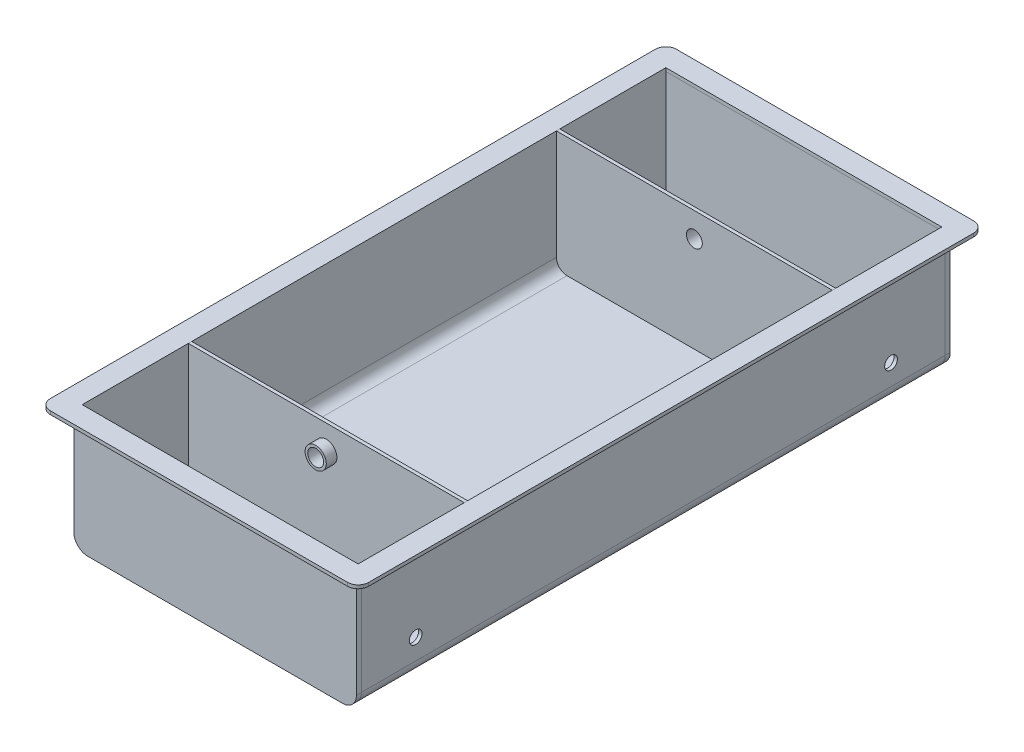
SolidWorks part; units mm, degrees
material "5052-H32"
ref_plane "Front Plane" through (0, 0, 0) normal (0, 0, 1) x (1, 0, 0)
ref_plane "Top Plane" through (0, 0, 0) normal (0, 1, 0) x (1, 0, 0)
ref_plane "Right Plane" through (0, 0, 0) normal (1, 0, 0) x (0, 0, -1)
sketch "Sketch2" plane through (0, 0, 0) normal (0, 0, 1) x (1, 0, 0)
  line L0 (-130, 0) -> (130, 0)
  line L1 (-130, 0) -> (-130, 110)
  line L2 (130, 0) -> (130, 110)
  line L3 (-133.175, -3.175) -> (-133.175, 110)
  line L4 (-133.175, -3.175) -> (133.175, -3.175)
  line L5 (133.175, -3.175) -> (133.175, 110)
  line L6 (-133.175, 110) -> (-130, 110)
  line L7 (130, 110) -> (133.175, 110)
  point P4 (0, 0)
  dimension "D1" = 260
  dimension "D3" = 110
  dimension "D4" = 110
  dimension "D2" = 3.175
  dimension "D5" = 3.175
  dimension "D6" = 3.175
extrude "Interior Dim" add sketch "Sketch2" against normal blind 550
fillet "Fillet2" radius 10 2 edges at (-130, 0, -275) (130, 0, -275)
fillet "Fillet3" radius 13.175 2 edges at (-133.175, -3.175, -275) (133.175, -3.175, -275)
ref_plane "Plane1" through (0, 0, 0) normal (0, 0, 1) x (1, 0, 0)
sketch "Sketch4" plane through (0, 0, 0) normal (0, 0, 1) x (1, 0, 0)
  line L0 (-130, 110) -> (130, 110)
  line L9 (-120, -3.175) -> (120, -3.175)
  line L10 (133.175, 10) -> (133.175, 110)
  line L11 (133.175, 110) -> (130, 110)
  line L12 (130, 110) -> (130, 10)
  line L13 (120, 0) -> (-120, 0)
  line L14 (-130, 10) -> (-130, 110)
  line L15 (-130, 110) -> (-133.175, 110)
  line L16 (-133.175, 110) -> (-133.175, 10)
  line L17 (-120, -3.175) -> (120, -3.175)
  line L18 (133.175, 10) -> (133.175, 110)
  line L19 (133.175, 110) -> (130, 110)
  line L23 (-130, 110) -> (-133.175, 110)
  line L24 (-133.175, 110) -> (-133.175, 10)
  arc A4 (120, -3.175) -> (133.175, 10) centre (120, 10) ccw
  arc A5 (120, 0) -> (130, 10) centre (120, 10) ccw
  arc A6 (-130, 10) -> (-120, 0) centre (-120, 10) ccw
  arc A7 (120, -3.175) -> (133.175, 10) centre (120, 10) ccw
  arc A9 (-133.175, 10) -> (-120, -3.175) centre (-120, 10) ccw
  arc A10 (-133.175, 10) -> (-120, -3.175) centre (-120, 10) ccw
  dimension "D1" = 0
extrude "Endcap1" add sketch "Sketch4" along normal blind 4.7625 separate body
ref_plane "Plane2" through (0, 0, -550) normal (0, 0, -1) x (-1, 0, 0)
sketch "Sketch5" plane through (0, 0, -550) normal (0, 0, -1) x (-1, 0, 0)
  line L8 (133.175, 110) -> (-133.175, 110)
  line L16 (-133.175, 110) -> (-133.175, 10)
  line L17 (-120, -3.175) -> (120, -3.175)
  line L18 (133.175, 10) -> (133.175, 110)
  line L19 (133.175, 110) -> (130, 110)
  line L20 (130, 110) -> (130, 10)
  line L21 (120, 0) -> (-120, 0)
  line L22 (-130, 10) -> (-130, 110)
  line L23 (-130, 110) -> (-133.175, 110)
  line L24 (-133.175, 110) -> (-133.175, 10)
  line L25 (-120, -3.175) -> (120, -3.175)
  line L26 (133.175, 10) -> (133.175, 110)
  arc A6 (-133.175, 10) -> (-120, -3.175) centre (-120, 10) ccw
  arc A7 (-133.175, 10) -> (-120, -3.175) centre (-120, 10) ccw
  arc A8 (120, 0) -> (130, 10) centre (120, 10) ccw
  arc A9 (-130, 10) -> (-120, 0) centre (-120, 10) ccw
  arc A12 (120, -3.175) -> (133.175, 10) centre (120, 10) ccw
  arc A13 (120, -3.175) -> (133.175, 10) centre (120, 10) ccw
  dimension "D1" = 0
ref_plane "Compartment1" through (0, 0, -100) normal (0, 0, -1) x (-1, 0, 0)
sketch "Sketch7" plane through (0, 0, -100) normal (0, 0, -1) x (-1, 0, 0)
  line L1 (130, 110) -> (-130, 110)
  line L10 (-120, -3.175) -> (120, -3.175)
  line L11 (-133.175, 110) -> (-133.175, 10)
  line L12 (-130, 110) -> (-133.175, 110)
  line L13 (-130, 10) -> (-130, 110)
  line L14 (120, 0) -> (-120, 0)
  line L15 (130, 110) -> (130, 10)
  line L16 (133.175, 110) -> (130, 110)
  line L17 (133.175, 10) -> (133.175, 110)
  line L21 (-130, 10) -> (-130, 110)
  line L22 (120, 0) -> (-120, 0)
  line L23 (130, 110) -> (130, 10)
  arc A5 (-130, 10) -> (-120, 0) centre (-120, 10) ccw
  arc A6 (120, 0) -> (130, 10) centre (120, 10) ccw
  arc A7 (-133.175, 10) -> (-120, -3.175) centre (-120, 10) ccw
  arc A8 (120, -3.175) -> (133.175, 10) centre (120, 10) ccw
  arc A9 (-130, 10) -> (-120, 0) centre (-120, 10) ccw
  arc A10 (120, 0) -> (130, 10) centre (120, 10) ccw
  dimension "D1" = 0
extrude "Compartment1_Boss" add sketch "Sketch7" along normal blind 3.175 separate body contours L22 A10 L23 L1 L21 A9 region at (0, 55.0793, -100)
ref_plane "Plane5" through (0, 110, 0) normal (0, 1, 0) x (1, 0, 0)
sketch "Sketch9" plane through (0, 110, 0) normal (0, 1, 0) x (1, 0, 0)
  line L0 (62.2463, 550) -> (-62.2463, 550) construction
  line L1 (-130, 550) -> (130, 550)
  line L2 (-130, 550) -> (-130, 0)
  line L3 (-130, 0) -> (130, 0)
  line L4 (130, 550) -> (130, 0)
  line L5 (-130, 0) -> (-130, 550) construction
  line L6 (-62.2463, 0) -> (62.2463, 0) construction
  line L7 (130, 550) -> (130, 0) construction
  line L8 (-150, 570) -> (-150, -20)
  line L9 (-150, -20) -> (150, -20)
  line L10 (150, 570) -> (150, -20)
  line L11 (-150, 570) -> (150, 570)
extrude "Lid_Flange" add sketch "Sketch9" along normal blind 3.175 separate body contours L11 L8 L9 L10 L1 L4 region at (0, 110, -563.3811)
fillet "Fillet4" radius 10 4 edges at (-150, 111.5875, -570) (150, 111.5875, -570) (150, 111.5875, 20) (-150, 111.5875, 20)
extrude "Endcap2" add sketch "Sketch5" along normal blind 4.7625 separate body
ref_plane "Compartment2" through (0, 0, -450) normal (0, 0, 1) x (1, 0, 0)
sketch "Sketch13" plane through (0, 0, -450) normal (0, 0, 1) x (1, 0, 0)
  line L0 (130, 110) -> (-130, 110)
  line L1 (133.175, 110) -> (130, 110) construction
  line L2 (130, 110) -> (130, 10) construction
  line L3 (-140, 110) -> (140, 110) construction
  line L4 (-130, 10) -> (-130, 110) construction
  line L5 (130, 110) -> (130, 10)
  line L6 (-130, 110) -> (-130, 10)
  line L7 (120, 0) -> (-120, 0)
  arc A0 (120, 0) -> (130, 10) centre (120, 10) ccw construction
  arc A1 (-130, 10) -> (-120, 0) centre (-120, 10) ccw construction
  arc A2 (-130, 10) -> (-120, 0) centre (-120, 10) ccw
  arc A3 (130, 10) -> (120, 0) centre (120, 10) cw
  dimension "D1" = 110
extrude "Compartment2_Boss" add sketch "Sketch13" along normal blind 3.175
sketch "Sketch16" plane through (-133.175, 0, 0) normal (-1, 0, 0) x (0, 0, 1)
  line L0 (-550, 0) -> (-450, 0) construction
  line L1 (-550, 110) -> (-550, 10) construction
  line L2 (0, 110) -> (0, 10) construction
  line L3 (-51, 29.5) -> (-499, 29.5) construction
  circle A0 centre (-499, 29.5) radius 6
  circle A1 centre (-51, 29.5) radius 6
  dimension "D1" = 12
  dimension "D4" = 12
  dimension "D2" = 29.5
  dimension "D3" = 51
  dimension "D5" = 51
extrude "Bearing_holes" cut sketch "Sketch16" against normal through all
sketch "Sketch17" plane through (0, 0, -450) normal (0, 0, -1) x (-1, 0, 0)
  line L0 (142.7388, 110) -> (-142.7388, 110) construction
  line L1 (130, 110) -> (130, 10) construction
  circle A0 centre (0, 90) radius 7.5
  circle A1 centre (0, 90) radius 10
  dimension "D1" = 15
  dimension "D4" = 20
  dimension "D2" = 20
  dimension "D3" = 130
extrude "Wire_Passthrough" cut sketch "Sketch17" against normal up to surface (350 mm away) contours A0 region at (0, 90, -450) up to face at (0, 39.3096, -100)
sketch "Sketch18" plane through (0, 110, 0) normal (0, 1, 0) x (1, 0, 0)
  line L1 (-130, 450) -> (130, 450)
  line L2 (-130, 450) -> (-130, 446.825)
  line L3 (-130, 446.825) -> (130, 446.825)
  line L4 (130, 450) -> (130, 446.825)
  line L5 (-130, 103.175) -> (130, 103.175)
  line L6 (-130, 103.175) -> (-130, 100)
  line L7 (-130, 100) -> (130, 100)
  line L8 (130, 103.175) -> (130, 100)
extrude "Boss-Extrude1" add sketch "Sketch18" along normal blind 3.18
extrude "Wire_Tube_2" add sketch "Sketch17<3>" along normal blind 10
sketch "Sketch17<3>" plane through (0, 0, -450) normal (0, 0, -1) x (-1, 0, 0) same geometry as "Sketch17"
sketch "Sketch19" plane through (0, 0, -100) normal (0, 0, 1) x (1, 0, 0)
  circle A0 centre (0, 90) radius 10
  circle M1 centre (0, 90) radius 7.5
  dimension "D1" = 20
extrude "Wire_Tube_1" add sketch "Sketch19" along normal blind 10 contours A0 M1 region at (-9.7172, 90, -100)
sketch "Sketch20" plane through (0, 110, 175) normal (0, 1, 0) x (1, 0, 0)
  line L0 (130, 450) -> (-130, 450) construction
  line L1 (-130, 725) -> (130, 725) construction
  line L2 (-130, 725) -> (-130, 175) construction
  line L3 (-130, 175) -> (130, 175) construction
  line L4 (130, 725) -> (130, 175) construction
  line L5 (130, 621.825) -> (130, 278.175) construction
  line L7 (0, 450) -> (0, 175) construction
  line L8 (-150, 745) -> (-150, 155) construction
  line L9 (-150, 155) -> (150, 155) construction
  line L10 (150, 745) -> (150, 155) construction
  line L11 (-150, 745) -> (150, 745) construction
  line L12 (-130, 621.825) -> (-130, 278.175) construction
  circle A0 centre (-140, 165) radius 2.5
  circle A2 centre (-140, 217) radius 2.5
  circle A3 centre (-140, 269) radius 2.5
  circle A4 centre (-140, 321) radius 2.5
  circle A5 centre (-140, 373) radius 2.5
  circle A6 centre (-140, 425) radius 2.5
  circle A7 centre (-140, 477) radius 2.5
  circle A8 centre (-140, 529) radius 2.5
  circle A9 centre (-140, 581) radius 2.5
  circle A10 centre (-140, 633) radius 2.5
  circle A16 centre (-140, 685) radius 2.5
  circle A17 centre (-84, 685) radius 2.5
  circle A18 centre (-28, 685) radius 2.5
  circle A19 centre (28, 685) radius 2.5
  circle A20 centre (84, 685) radius 2.5
  circle A21 centre (140, 685) radius 2.5
  circle A22 centre (140, 633) radius 2.5
  circle A23 centre (140, 581) radius 2.5
  circle A24 centre (140, 529) radius 2.5
  circle A25 centre (140, 477) radius 2.5
  circle A26 centre (140, 425) radius 2.5
  circle A27 centre (140, 373) radius 2.5
  circle A28 centre (140, 321) radius 2.5
  circle A29 centre (140, 269) radius 2.5
  circle A30 centre (140, 217) radius 2.5
  circle A31 centre (140, 165) radius 2.5
  circle A37 centre (84, 165) radius 2.5
  circle A38 centre (28, 165) radius 2.5
  circle A39 centre (-28, 165) radius 2.5
  circle A40 centre (-84, 165) radius 2.5
  dimension "D4" = 5
  dimension "D3" = 10
  dimension "D9" = 275
  dimension "D2" = 550
  dimension "D10" = 10
  dimension "D11" = 260
  dimension "D1" = 20
  dimension "D8" = 11
  dimension "D5" = 6
  dimension "D6" = 11
  dimension "D7" = 5
extrude "Bolt_Holes" [suppressed] cut sketch "Sketch20" along normal up to next
equation "\"L\"= 550"
equation "\"W\"= 260"
equation "\"D1@Sketch2\"=\"W\""
equation "\"D1@Interior Dim\" = \"L\""
equation "\"H\"= 110"
equation "\"D3@Sketch2\"=\"H\""
equation "\"D4@Sketch2\"=\"H\""
equation "\"Compartment Width\"= 100"
equation "\"D1@Compartment2\"=\"Compartment Width\""
equation "\"D1@Compartment1\"=\"Compartment Width\""
equation "\"D1@Sketch13\"=\"H\""
equation "\"D3@Sketch17\"=\"W\"/2"
equation "\"T\"= 4.7625 * 2 / 3"
equation "\"D1@Lid_Flange\"=\"T\""
equation "\"D1@Fillet3\"=\"T\"+10"
equation "\"D1@Compartment1_Boss\"=\"T\""
equation "\"D1@Compartment2_Boss\"=\"T\""
equation "\"D2@Sketch20\"=\"L\""
equation "\"D11@Sketch20\"=\"W\""
equation "\"D9@Sketch20\"=\"L\"/2"
